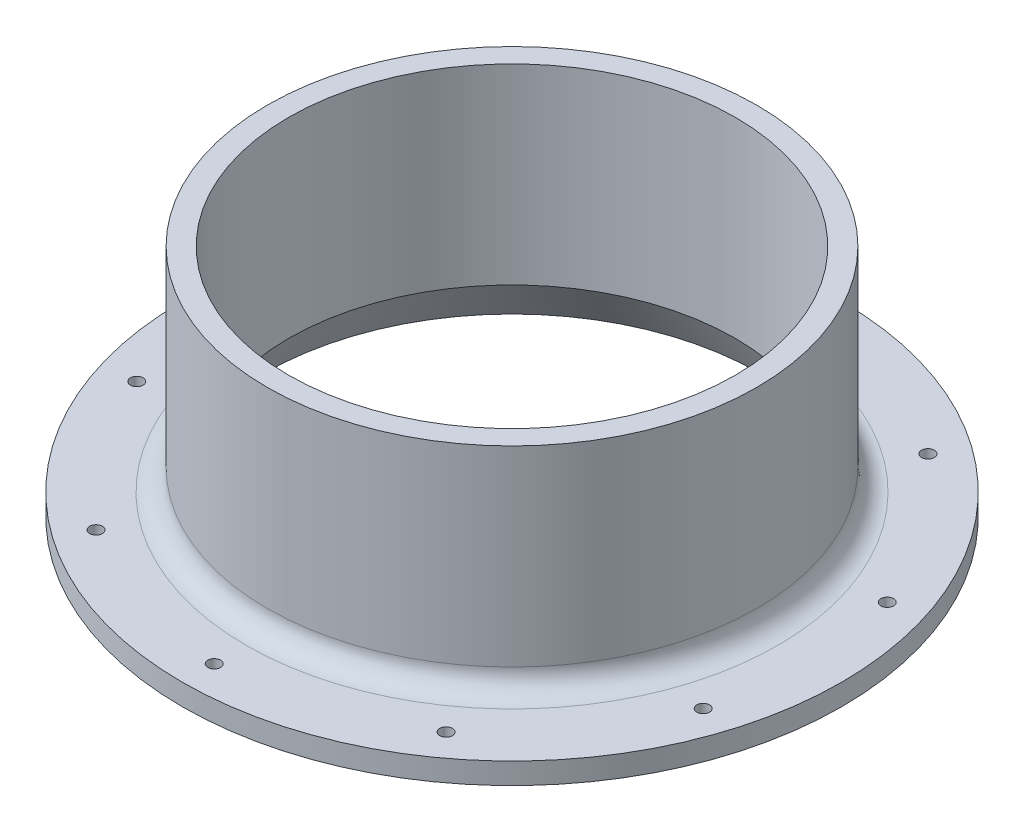
SolidWorks part; units mm, degrees
ref_plane "Front Plane" through (0, 0, 0) normal (0, 0, 1) x (1, 0, 0)
ref_plane "Top Plane" through (0, 0, 0) normal (0, 1, 0) x (1, 0, 0)
ref_plane "Right Plane" through (0, 0, 0) normal (1, 0, 0) x (0, 0, -1)
sketch "Sketch2" plane through (0, 0, 0) normal (0, 1, 0) x (1, 0, 0)
  line L0 (0, 0) -> (0, 88.9) construction
  line L5 (0, 88.9) -> (0, 98.425) construction
  circle A0 centre (0, 0) radius 73.025
  circle A9 centre (0, 0) radius 66.675
  circle A10 centre (0, 0) radius 98.425
  circle A11 centre (0, 88.9) radius 1.9
  point P37 (0, 0)
  dimension "D1" = 146.05
  dimension "D4" = 3.8
  dimension "D9" = 6.35
  dimension "D2" = 25.4
  dimension "D3" = 9.525
extrude "Boss-Extrude1" add sketch "Sketch2" against normal blind 6.35 contours A10 A11 A0 | A11 | A0 A9 region at (-70.9595, 0, 0) region at (-95.6411, 0, 0) region at (0, 0, -88.9)
extrude "Boss-Extrude2" add sketch "Sketch2<3>" along normal blind 63.5 contours A0 A9 | A0 A9 region at (-70.9595, 0, 0)
sketch "Sketch2<3>" plane through (0, 0, 0) normal (0, 1, 0) x (1, 0, 0) same geometry as "Sketch2"
fillet "Fillet1" radius 6.35 1 edges at (0, 0, 73.025)
fillet "Fillet2" [suppressed] radius 12.7
chamfer "Chamfer1" [suppressed] distance 3.175 angle 45
extrude "Cut-Extrude2" cut sketch "Sketch2<5>" against normal through all contours A11
sketch "Sketch2<5>" plane through (0, 0, 0) normal (0, 1, 0) x (1, 0, 0) same geometry as "Sketch2"
chamfer "Chamfer2" distance 2.032 angle 45 1 edges at (0, -6.35, -87)
ref_axis "Axis1" through (0, 0, 0) along (0, 1, 0)
pattern_circular "CirPattern1" count 10 over 360 about axis through (0, 0, 0) along (0, 1, 0) of "Cut-Extrude2", "Chamfer2"
chamfer "Chamfer3" distance 12.7 angle 30 1 edges at (0, -6.35, 66.675) first distance on face at (0, -6.35, 66.675)
